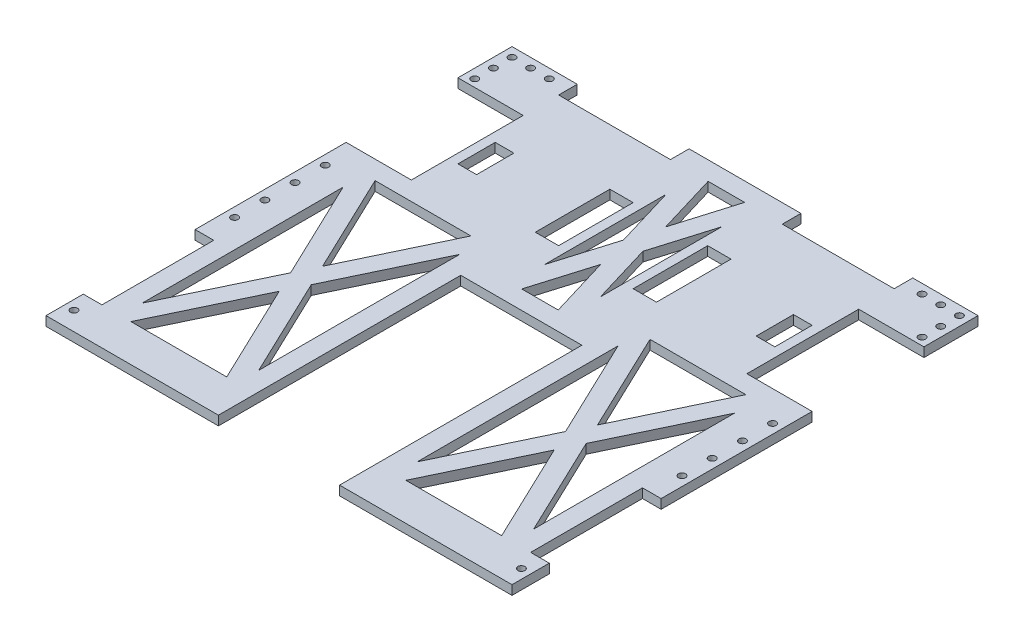
SolidWorks part; units mm, degrees
material "7050-T73510"
ref_plane "Front Plane" through (0, 0, 0) normal (0, 0, 1) x (1, 0, 0)
ref_plane "Top Plane" through (0, 0, 0) normal (0, 1, 0) x (1, 0, 0)
ref_plane "Right Plane" through (0, 0, 0) normal (1, 0, 0) x (0, 0, -1)
sketch "Sketch1" plane through (0, 0, 0) normal (0, 1, 0) x (1, 0, 0)
  line L0 (0, -55) -> (0, 55) construction
  line L1 (-158.75, -76.2) -> (158.75, -76.2)
  line L2 (-158.75, -76.2) -> (-158.75, 76.2)
  line L3 (-158.75, 76.2) -> (158.75, 76.2)
  line L4 (158.75, -76.2) -> (158.75, 76.2)
  line L5 (-158.75, -76.2) -> (158.75, 76.2) construction
  line L6 (-158.75, 76.2) -> (158.75, -76.2) construction
  line L7 (-158.75, -76.2) -> (-25.4, -76.2)
  line L8 (-158.75, -76.2) -> (-158.75, -241.3)
  line L9 (-158.75, -241.3) -> (-25.4, -241.3)
  line L10 (-25.4, -76.2) -> (-25.4, -241.3)
  line L11 (25.4, -76.2) -> (25.4, -241.3)
  line L12 (158.75, -241.3) -> (25.4, -241.3)
  line L13 (158.75, -76.2) -> (158.75, -241.3)
  line L14 (158.75, -76.2) -> (25.4, -76.2)
  line L15 (-41.275, -76.2) -> (-41.275, -241.3)
  line L16 (41.275, -76.2) -> (41.275, -241.3)
  point P0 (0, 0)
  dimension "D1" = 317.5
  dimension "D2" = 152.4
  dimension "D3" = 317.5
  dimension "D4" = 50.8
  dimension "D5" = 15.875
extrude "Boss-Extrude1" add sketch "Sketch1" along normal blind 6.35 contours L15 L1 L8 L9 | L14 L16 L12 L13 | L1 L7 L14 L4 L3 L2 region at (0, 0, 0) region at (-100.0125, 0, 158.75) region at (100.0125, 0, 158.75)
sketch "Sketch2" plane through (0, 6.35, 0) normal (0, 1, 0) x (1, 0, 0)
  line L0 (158.75, -241.3) -> (158.75, 76.2) construction
  line L1 (158.75, 39.37) -> (114.3, 39.37)
  line L2 (158.75, 39.37) -> (158.75, -36.83)
  line L3 (158.75, -36.83) -> (114.3, -36.83)
  line L4 (114.3, 39.37) -> (114.3, -36.83)
  line L5 (-158.75, 76.2) -> (158.75, 76.2) construction
  line L6 (158.75, -139.7) -> (146.05, -139.7)
  line L7 (158.75, -139.7) -> (158.75, -215.9)
  line L8 (158.75, -215.9) -> (146.05, -215.9)
  line L9 (146.05, -139.7) -> (146.05, -215.9)
  line L10 (0, -3.4925) -> (0, 3.4925) construction
  line L11 (-158.75, -215.9) -> (-146.05, -215.9)
  line L12 (-146.05, -139.7) -> (-146.05, -215.9)
  line L13 (-158.75, -139.7) -> (-146.05, -139.7)
  line L14 (-158.75, -139.7) -> (-158.75, -215.9)
  line L15 (-158.75, -36.83) -> (-114.3, -36.83)
  line L16 (-114.3, 39.37) -> (-114.3, -36.83)
  line L17 (-158.75, 39.37) -> (-114.3, 39.37)
  line L18 (-158.75, 39.37) -> (-158.75, -36.83)
  line L19 (-114.3, 63.5) -> (-38.1, 63.5)
  line L20 (114.3, 76.2) -> (38.1, 76.2)
  line L21 (114.3, 76.2) -> (114.3, 63.5)
  line L22 (114.3, 63.5) -> (38.1, 63.5)
  line L23 (38.1, 76.2) -> (38.1, 63.5)
  line L24 (-38.1, 76.2) -> (-38.1, 63.5)
  line L25 (-114.3, 76.2) -> (-38.1, 76.2)
  line L26 (-114.3, 76.2) -> (-114.3, 63.5)
  dimension "D1" = 44.45
  dimension "D2" = 12.7
  dimension "D3" = 76.2
  dimension "D4" = 76.2
  dimension "D5" = 36.83
  dimension "D6" = 215.9
  dimension "D7" = 76.2
  dimension "D8" = 12.7
  dimension "D9" = 76.2
extrude "Cut-Extrude1" cut sketch "Sketch2" against normal through all
sketch "Sketch4" plane through (0, 6.35, 0) normal (0, 1, 0) x (1, 0, 0)
  line L0 (41.275, -76.2) -> (41.275, -241.3) construction
  line L1 (53.975, -215.9) -> (133.35, -215.9)
  line L2 (53.975, -215.9) -> (53.975, -49.53)
  line L3 (53.975, -49.53) -> (133.35, -49.53)
  line L4 (133.35, -215.9) -> (133.35, -49.53)
  line L5 (146.05, -139.7) -> (146.05, -215.9) construction
  line L6 (158.75, -241.3) -> (41.275, -241.3) construction
  line L7 (53.975, -215.9) -> (133.35, -49.53) construction
  line L8 (53.975, -49.53) -> (133.35, -215.9) construction
  line L9 (133.35, -201.1532) -> (61.0107, -49.53)
  line L10 (126.3143, -215.9) -> (53.975, -64.2768)
  line L11 (53.975, -201.1532) -> (126.3143, -49.53)
  line L12 (61.0107, -215.9) -> (133.35, -64.2768)
  line L13 (114.3, -36.83) -> (158.75, -36.83) construction
  line L14 (0, -3.4925) -> (0, 3.4925) construction
  line L15 (-53.975, -201.1532) -> (-126.3143, -49.53)
  line L16 (-126.3143, -215.9) -> (-53.975, -64.2768)
  line L17 (-133.35, -201.1532) -> (-61.0107, -49.53)
  line L18 (-61.0107, -215.9) -> (-133.35, -64.2768)
  line L19 (-53.975, -49.53) -> (-133.35, -49.53)
  line L20 (-133.35, -215.9) -> (-133.35, -49.53)
  line L21 (-53.975, -215.9) -> (-133.35, -215.9)
  line L22 (-53.975, -215.9) -> (-53.975, -49.53)
  point P18 (116.9135, -166.7022)
  dimension "D1" = 12.7
  dimension "D2" = 12.7
  dimension "D3" = 25.4
  dimension "D4" = 12.7
  dimension "D5" = 12.7
extrude "Cut-Extrude3" cut sketch "Sketch4" against normal through all contours L12 L9 L4 | L12 L1 L10 | L2 L11 L10 | L9 L11 L3 | L21 L18 L16 | L20 L17 L18 | L17 L19 L15 | L15 L22 L16 region at (93.6625, 6.35, 193.0873) region at (64.8589, 6.35, 132.715) region at (122.4661, 6.35, 132.715) region at (93.6625, 6.35, 72.3427) region at (-64.8589, 6.35, 132.715) region at (-93.6625, 6.35, 72.3427) region at (-93.6625, 6.35, 193.0873) region at (-122.4661, 6.35, 132.715)
sketch "Sketch3" plane through (0, 6.35, 0) normal (0, 1, 0) x (1, 0, 0)
  line L0 (-41.275, -76.2) -> (41.275, -76.2) construction
  line L1 (-41.275, -25.4) -> (-25.4, -25.4)
  line L2 (-41.275, -25.4) -> (-41.275, 25.4)
  line L3 (-41.275, 25.4) -> (-25.4, 25.4)
  line L4 (-25.4, -25.4) -> (-25.4, 25.4)
  line L5 (0, -3.4925) -> (0, 3.4925) construction
  line L6 (41.275, 25.4) -> (25.4, 25.4)
  line L7 (25.4, -25.4) -> (25.4, 25.4)
  line L8 (41.275, -25.4) -> (25.4, -25.4)
  line L9 (41.275, -25.4) -> (41.275, 25.4)
  line L10 (114.3, 39.37) -> (114.3, -36.83) construction
  line L11 (95.25, 13.97) -> (107.95, 13.97)
  line L12 (95.25, 13.97) -> (95.25, -11.43)
  line L13 (95.25, -11.43) -> (107.95, -11.43)
  line L14 (107.95, 13.97) -> (107.95, -11.43)
  line L15 (38.1, 63.5) -> (114.3, 63.5) construction
  line L16 (-95.25, -11.43) -> (-107.95, -11.43)
  line L17 (-107.95, 13.97) -> (-107.95, -11.43)
  line L18 (-95.25, 13.97) -> (-107.95, 13.97)
  line L19 (-95.25, 13.97) -> (-95.25, -11.43)
  dimension "D1" = 50.8
  dimension "D2" = 15.875
  dimension "D3" = 50.8
  dimension "D4" = 50.8
  dimension "D5" = 25.4
  dimension "D6" = 12.7
  dimension "D7" = 6.35
  dimension "D8" = 49.53
extrude "Cut-Extrude2" cut sketch "Sketch3" against normal through all
sketch "Sketch6" plane through (0, 6.35, 0) normal (0, 1, 0) x (1, 0, 0)
  line L0 (-25.4, -25.4) -> (-25.4, 25.4) construction
  line L1 (-19.05, 63.5) -> (19.05, 63.5)
  line L2 (-19.05, 63.5) -> (-19.05, -63.5)
  line L3 (-19.05, -63.5) -> (19.05, -63.5)
  line L4 (19.05, 63.5) -> (19.05, -63.5)
  line L5 (25.4, 25.4) -> (25.4, -25.4) construction
  line L6 (-38.1, 76.2) -> (38.1, 76.2) construction
  line L7 (-41.275, -76.2) -> (41.275, -76.2) construction
  line L8 (-19.05, -63.5) -> (19.05, 63.5) construction
  line L9 (19.05, -63.5) -> (-19.05, 63.5) construction
  line L10 (12.4204, -63.5) -> (-19.05, 41.4014)
  line L11 (-12.4204, 63.5) -> (19.05, -41.4014)
  line L12 (-19.05, -41.4014) -> (12.4204, 63.5)
  line L13 (19.05, 41.4014) -> (-12.4204, -63.5)
  dimension "D1" = 6.35
  dimension "D2" = 6.35
  dimension "D3" = 12.7
  dimension "D4" = 12.7
  dimension "D5" = 12.7
  dimension "D6" = 12.7
extrude "Cut-Extrude5" cut sketch "Sketch6" against normal through all contours L10 L13 L3 | L4 L13 L11 | L2 L12 L10 | L11 L12 L1 region at (0, 6.35, -49.6995) region at (-14.9099, 6.35, 0) region at (14.9099, 6.35, 0) region at (0, 6.35, 49.6995)
sketch "Sketch7" plane through (0, 6.35, 0) normal (0, 1, 0) x (1, 0, 0)
  line L0 (158.75, -139.7) -> (146.05, -139.7) construction
  line L1 (158.75, -139.7) -> (158.75, -36.83) construction
  line L2 (0, -3.4925) -> (0, 3.4925) construction
  line L3 (158.75, -241.3) -> (41.275, -241.3) construction
  line L5 (114.3, 76.2) -> (158.75, 76.2) construction
  circle A0 centre (152.4, -119.126) radius 2.413
  circle A1 centre (152.4, -98.552) radius 2.413
  circle A2 centre (152.4, -77.978) radius 2.413
  circle A3 centre (152.4, -57.404) radius 2.413
  circle A4 centre (-152.4, -57.404) radius 2.413
  circle A5 centre (-152.4, -77.978) radius 2.413
  circle A6 centre (-152.4, -98.552) radius 2.413
  circle A7 centre (-152.4, -119.126) radius 2.413
  circle A8 centre (152.4, -228.6) radius 2.413
  circle A9 centre (152.4, 69.85) radius 2.413
  circle A10 centre (139.7, 69.85) radius 2.413
  circle A11 centre (127, 69.85) radius 2.413
  circle A12 centre (152.4, 57.15) radius 2.413
  circle A13 centre (152.4, 44.45) radius 2.413
  circle A14 centre (-152.4, 44.45) radius 2.413
  circle A15 centre (-152.4, 57.15) radius 2.413
  circle A16 centre (-127, 69.85) radius 2.413
  circle A17 centre (-139.7, 69.85) radius 2.413
  circle A18 centre (-152.4, 69.85) radius 2.413
  circle A19 centre (-152.4, -228.6) radius 2.413
  dimension "D1" = 4.826
  dimension "D3" = 6.35
  dimension "D5" = 12.7
  dimension "D6" = 6.35
  dimension "D2" = 20.574
  dimension "D8" = 3
  dimension "D4" = 4
  dimension "D7" = 3
extrude "Cut-Extrude6" cut sketch "Sketch7" against normal through all
sketch "Sketch5" plane through (0, 6.35, 0) normal (0, 1, 0) x (1, 0, 0)
  line L0 (0, -3.4925) -> (0, 3.4925) construction
  line L2 (-38.1, 76.2) -> (38.1, 76.2) construction
  line L3 (41.275, -25.4) -> (41.275, 25.4) construction
  line L4 (114.3, 63.5) -> (38.1, 63.5) construction
  circle A0 centre (12.7, 63.5) radius 6.35
  circle A1 centre (12.7, 50.8) radius 6.35
  circle A2 centre (12.7, 38.1) radius 6.35
  circle A3 centre (12.7, 25.4) radius 6.35
  circle A4 centre (12.7, 12.7) radius 6.35
  circle A11 centre (0, 50.8) radius 6.35
  circle A12 centre (0, 38.1) radius 6.35
  circle A13 centre (0, 25.4) radius 6.35
  circle A14 centre (0, 12.7) radius 6.35
  circle A21 centre (-12.7, 50.8) radius 6.35
  circle A22 centre (-12.7, 38.1) radius 6.35
  circle A23 centre (-12.7, 25.4) radius 6.35
  circle A24 centre (-12.7, 12.7) radius 6.35
  circle A31 centre (0, 63.5) radius 6.35
  circle A32 centre (-12.7, 63.5) radius 6.35
  circle A33 centre (53.975, 50.8) radius 3.175
  circle A34 centre (66.675, 50.8) radius 3.175
  circle A35 centre (79.375, 50.8) radius 3.175
  circle A36 centre (66.675, 38.1) radius 3.175
  circle A37 centre (79.375, 38.1) radius 3.175
  circle A38 centre (66.675, 25.4) radius 3.175
  circle A39 centre (79.375, 25.4) radius 3.175
  circle A40 centre (66.675, 12.7) radius 3.175
  circle A41 centre (79.375, 12.7) radius 3.175
  circle A42 centre (66.675, 0) radius 3.175
  circle A43 centre (79.375, 0) radius 3.175
  circle A44 centre (66.675, -12.7) radius 3.175
  circle A45 centre (79.375, -12.7) radius 3.175
  circle A46 centre (66.675, -25.4) radius 3.175
  circle A47 centre (79.375, -25.4) radius 3.175
  circle A48 centre (66.675, -38.1) radius 3.175
  circle A49 centre (79.375, -38.1) radius 3.175
  circle A50 centre (53.975, 38.1) radius 3.175
  circle A51 centre (53.975, 25.4) radius 3.175
  circle A52 centre (53.975, 12.7) radius 3.175
  circle A53 centre (53.975, 0) radius 3.175
  circle A54 centre (53.975, -12.7) radius 3.175
  circle A55 centre (53.975, -25.4) radius 3.175
  circle A56 centre (53.975, -38.1) radius 3.175
  circle A57 centre (-53.975, -38.1) radius 3.175
  circle A58 centre (-53.975, -25.4) radius 3.175
  circle A59 centre (-53.975, -12.7) radius 3.175
  circle A60 centre (-53.975, 0) radius 3.175
  circle A61 centre (-53.975, 12.7) radius 3.175
  circle A62 centre (-53.975, 25.4) radius 3.175
  circle A63 centre (-53.975, 38.1) radius 3.175
  circle A64 centre (-79.375, -38.1) radius 3.175
  circle A65 centre (-66.675, -38.1) radius 3.175
  circle A66 centre (-79.375, -25.4) radius 3.175
  circle A67 centre (-66.675, -25.4) radius 3.175
  circle A68 centre (-79.375, -12.7) radius 3.175
  circle A69 centre (-66.675, -12.7) radius 3.175
  circle A70 centre (-79.375, 0) radius 3.175
  circle A71 centre (-66.675, 0) radius 3.175
  circle A72 centre (-79.375, 12.7) radius 3.175
  circle A73 centre (-66.675, 12.7) radius 3.175
  circle A74 centre (-79.375, 25.4) radius 3.175
  circle A75 centre (-66.675, 25.4) radius 3.175
  circle A76 centre (-79.375, 38.1) radius 3.175
  circle A77 centre (-66.675, 38.1) radius 3.175
  circle A78 centre (-79.375, 50.8) radius 3.175
  circle A79 centre (-66.675, 50.8) radius 3.175
  circle A80 centre (-53.975, 50.8) radius 3.175
  dimension "D1" = 12.7
  dimension "D6" = 6.35
  dimension "D2" = 12.7
  dimension "D3" = 12.7
  dimension "D7" = 12.7
  dimension "D8" = 12.7
  dimension "D4" = 5
  dimension "D5" = 3
  dimension "D9" = 3
  dimension "D10" = 8
